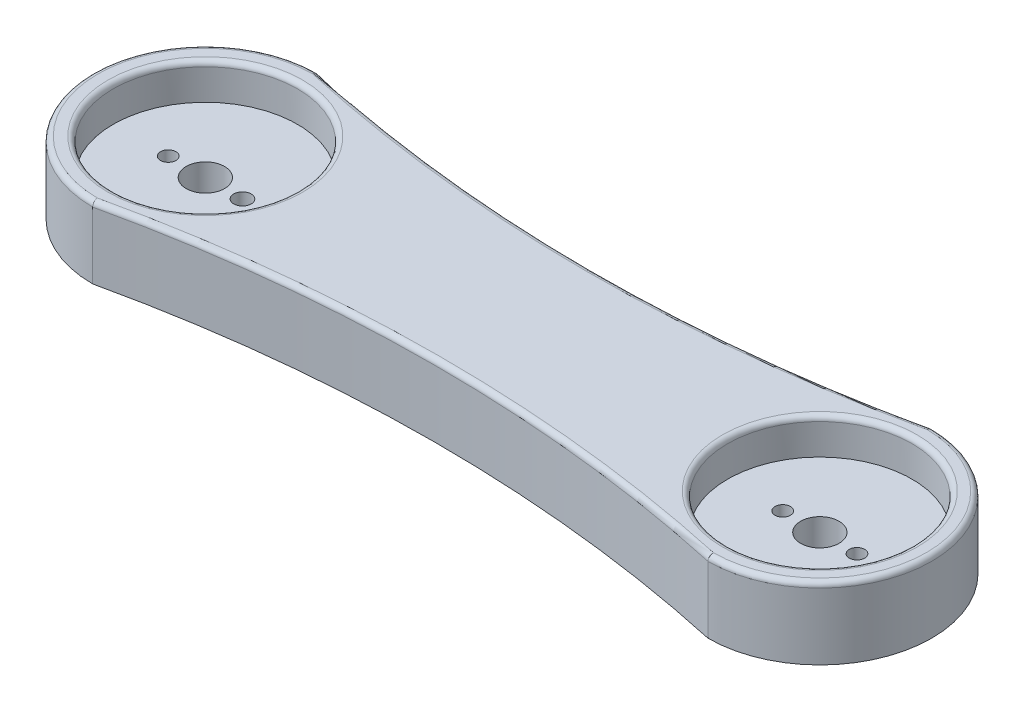
SolidWorks part; units mm, degrees
ref_plane "Alzado" through (0, 0, 0) normal (0, 0, 1) x (1, 0, 0)
ref_plane "Planta" through (0, 0, 0) normal (0, 1, 0) x (1, 0, 0)
ref_plane "Vista lateral" through (0, 0, 0) normal (1, 0, 0) x (0, 0, -1)
sketch "Croquis1" plane through (0, 0, 0) normal (0, 1, 0) x (1, 0, 0)
  line L0 (-199.5252, 0) -> (214.6407, 0) construction
  line L1 (-120, 39.9372) -> (-120, -53.0466) construction
  line L2 (0, 91.282) -> (0, -53.0466) construction
  arc A1 (-120, 22) -> (-120, -22) centre (-120, 0) ccw
  arc A4 (0, -21.8392) -> (0, 21.8392) centre (0, 0) ccw
  arc A11 (0, 21.8392) -> (-120, 22) centre (-59.6375, 292.5619) cw
  arc A12 (0, -21.8392) -> (-120, -22) centre (-59.6375, -292.5621) ccw
  dimension "D2" = 44
  dimension "D9" = 120
extrude "Saliente-Extruir7" add sketch "Croquis1" along normal blind 14
sketch "Croquis4" plane through (0, 14, 0) normal (0, 1, 0) x (1, 0, 0)
  circle A0 centre (-120, 0) radius 18
  arc A1 (-120, 22) -> (-120, -22) centre (-120, 0) ccw construction
  circle A2 centre (0, 0) radius 18
  arc A3 (0, -21.8392) -> (0, 21.8392) centre (0, 0) ccw construction
  dimension "D1" = 36
extrude "Cortar-Extruir1" cut sketch "Croquis4" against normal blind 7
sketch "Croquis5" plane through (0, 7, 0) normal (0, 1, 0) x (1, 0, 0)
  line L0 (-166.8967, 0) -> (42.2266, 0) construction
  circle A0 centre (-120, 0) radius 3.75
  circle A1 centre (-120, 0) radius 18 construction
  circle A2 centre (-127.25, 0) radius 1.5
  circle A4 centre (-112.75, 0) radius 1.7024
  point P9 (0, 0)
  dimension "D1" = 7.5
  dimension "D2" = 7.25
extrude "Cortar-Extruir3" cut sketch "Croquis5" against normal through all
sketch "Croquis6" plane through (0, 7, 0) normal (0, 1, 0) x (1, 0, 0)
  line L0 (-26.6932, 0) -> (30.7457, 0) construction
  circle A0 centre (0, 0) radius 3.75
  circle A1 centre (0, 0) radius 18 construction
  circle A2 centre (7.25, 0) radius 1.5
  circle A3 centre (-7.25, 0) radius 1.5
  point P9 (0, 0)
  dimension "D1" = 7.5
extrude "Cortar-Extruir4" cut sketch "Croquis6" against normal through all
fillet "Redondeo2" radius 1 6 edges at (0, 14, 18) (21.8392, 14, 0) (-60.0088, 14, -15.3485) (-120, 14, 18) (-142, 14, 0) (-60.0088, 14, 15.3486)
